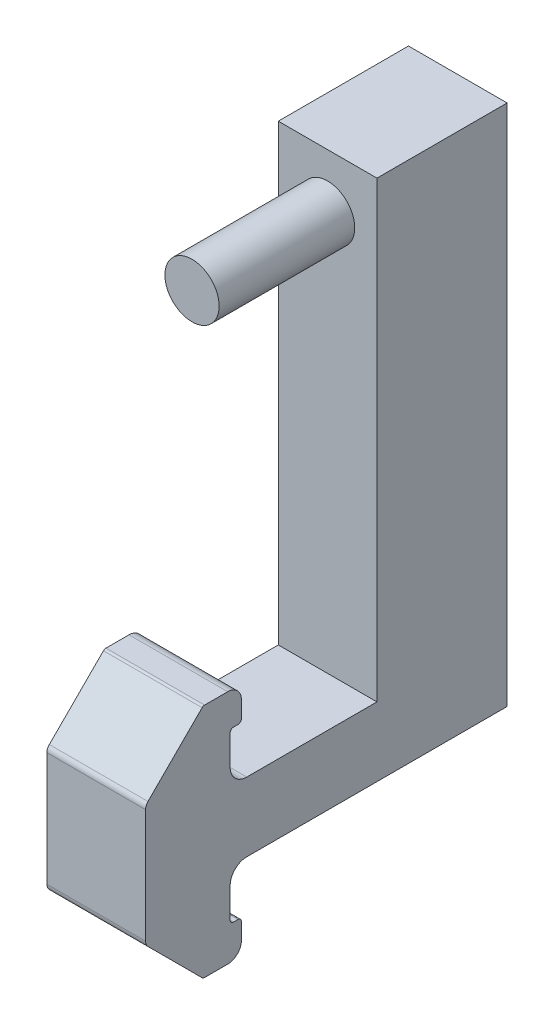
SolidWorks part; units mm, degrees
ref_plane "Front Plane" through (0, 0, 0) normal (0, 0, 1) x (1, 0, 0)
ref_plane "Top Plane" through (0, 0, 0) normal (0, 1, 0) x (1, 0, 0)
ref_plane "Right Plane" through (0, 0, 0) normal (1, 0, 0) x (0, 0, -1)
sketch "Sketch1" plane through (0, 0, 0) normal (0, 0, 1) x (1, 0, 0)
  circle A0 centre (0, 0) radius 2.5
  dimension "D1" = 5
extrude "Boss-Extrude1" add sketch "Sketch1" along normal blind 12.5 contours A0
sketch "Sketch2" plane through (0, 0, 0) normal (0, 0, -1) x (-1, 0, 0)
  line L0 (0, 0) -> (-4.5466, 0) construction
  line L1 (-4.5466, 0) -> (-4.5466, 5)
  line L2 (-4.5466, 5) -> (4.5466, 5)
  line L3 (4.5466, 5) -> (4.5466, 0)
  line L4 (4.5466, 0) -> (0, 0) construction
  line L5 (-4.5466, 0) -> (-4.5466, -40)
  line L6 (-4.5466, -40) -> (4.5466, -40)
  line L7 (4.5466, 0) -> (4.5466, -40)
  circle A0 centre (0, 0) radius 2.5 construction
  dimension "D1" = 5
  dimension "D2" = 40
extrude "Boss-Extrude2" add sketch "Sketch2" along normal blind 12
sketch "Sketch4" plane through (4.5466, 0, 0) normal (1, 0, 0) x (0, 0, -1)
  line L0 (-16.1163, -29.2187) -> (-21.1087, -34.2112)
  line L1 (-15.89, -50.875) -> (-13.76, -50.875)
  line L2 (-21.3319, -34.75) -> (-21.3319, -45.25)
  line L3 (-21.1087, -45.7888) -> (-16.1163, -50.7813)
  line L6 (0, -40) -> (-21.3319, -40) construction
  line L7 (-15.89, -29.125) -> (-13.76, -29.125)
  line L8 (-12.49, -30.395) -> (-12.49, -31.895)
  line L9 (-12.81, -32.215) -> (-13.21, -32.215)
  line L10 (-13.53, -32.535) -> (-13.53, -35.285)
  line L11 (-12, -36.815) -> (0, -36.815)
  line L12 (0, 5) -> (0, -40) construction
  line L13 (-12.49, -49.605) -> (-12.49, -48.105)
  line L14 (-12, -43.185) -> (0, -43.185)
  line L15 (-13.53, -47.465) -> (-13.53, -44.715)
  line L16 (-12.81, -47.785) -> (-13.21, -47.785)
  line L17 (0, -40) -> (0, -36.815)
  line L18 (0, -43.185) -> (12, -43.185)
  line L19 (12, -43.185) -> (12, -40)
  line L20 (12, -40) -> (0, -40)
  line L21 (0, -40) -> (0, -43.185) construction
  arc A0 (-21.1087, -45.7888) -> (-21.3319, -45.25) centre (-20.5699, -45.25) cw
  arc A1 (-21.1087, -34.2112) -> (-21.3319, -34.75) centre (-20.5699, -34.75) ccw
  arc A2 (-15.89, -50.875) -> (-16.1163, -50.7813) centre (-15.89, -50.555) cw
  arc A3 (-16.1163, -29.2187) -> (-15.89, -29.125) centre (-15.89, -29.445) cw
  arc A4 (-13.76, -29.125) -> (-12.49, -30.395) centre (-13.76, -30.395) cw
  arc A5 (-12.49, -31.895) -> (-12.81, -32.215) centre (-12.81, -31.895) cw
  arc A6 (-13.21, -32.215) -> (-13.53, -32.535) centre (-13.21, -32.535) ccw
  arc A7 (-13.53, -35.285) -> (-12, -36.815) centre (-12, -35.285) ccw
  arc A8 (-13.76, -50.875) -> (-12.49, -49.605) centre (-13.76, -49.605) ccw
  arc A9 (-13.53, -44.715) -> (-12, -43.185) centre (-12, -44.715) cw
  arc A10 (-13.21, -47.785) -> (-13.53, -47.465) centre (-13.21, -47.465) cw
  arc A11 (-12.49, -48.105) -> (-12.81, -47.785) centre (-12.81, -48.105) ccw
  point P16 (-16.1163, -74.0955)
  dimension "D1" = 0.762
  dimension "D4" = 0.32
  dimension "D6" = 0.32
  dimension "D7" = 1.27
  dimension "D9" = 0.32
  dimension "D11" = 0.32
  dimension "D12" = 1.53
  dimension "D14" = 21.75
  dimension "D25" = 135
  dimension "D26" = 135
  dimension "D2" = 10.5
  dimension "D5" = 2.13
  dimension "D8" = 1.5
  dimension "D10" = 0.4
  dimension "D13" = 12
  dimension "D18" = 2.75
extrude "Boss-Extrude3" add sketch "Sketch4" against normal up to surface (9.0932 mm away) up to face at (-4.5466, -17.5, -6)
